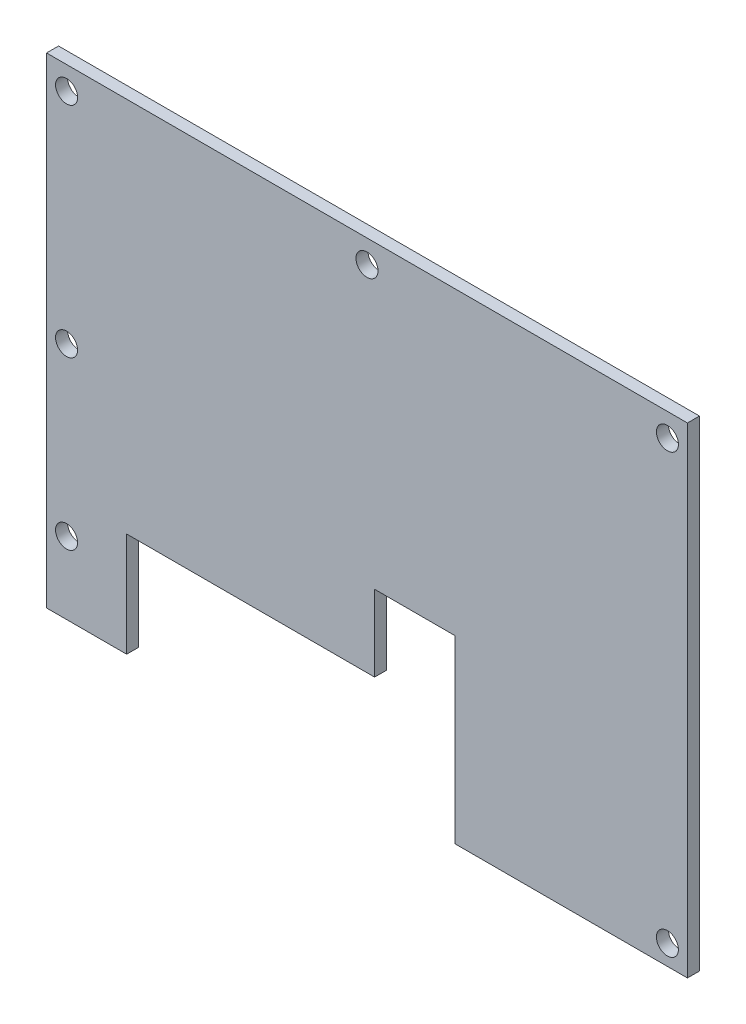
SolidWorks part; units mm, degrees
ref_plane "Front Plane" through (0, 0, 0) normal (0, 0, 1) x (1, 0, 0)
ref_plane "Top Plane" through (0, 0, 0) normal (0, 1, 0) x (1, 0, 0)
ref_plane "Right Plane" through (0, 0, 0) normal (1, 0, 0) x (0, 0, -1)
sketch "Sketch1" plane through (0, 0, 0) normal (0, 0, 1) x (1, 0, 0)
  line L1 (0, 0) -> (160, 0)
  line L2 (0, 0) -> (0, 120)
  line L3 (0, 120) -> (160, 120)
  line L4 (160, 0) -> (160, 120)
  dimension "D1" = 160
  dimension "D2" = 120
extrude "Boss-Extrude1" add sketch "Sketch1" along normal blind 3
sketch "Sketch2" plane through (0, 0, 3) normal (0, 0, 1) x (1, 0, 0)
  line L0 (0, 0) -> (160, 0) construction
  line L1 (81.9, 0) -> (102, 0)
  line L2 (81.9, 0) -> (81.9, 45)
  line L3 (81.9, 45) -> (102, 45)
  line L4 (102, 0) -> (102, 45)
  line L5 (160, 0) -> (160, 120) construction
  line L6 (0, 120) -> (0, 0) construction
  line L7 (20, 0) -> (81.9, 0)
  line L8 (20, 0) -> (20, 26)
  line L9 (20, 26) -> (81.9, 26)
  line L10 (81.9, 0) -> (81.9, 26)
  line M4 (0, 120) -> (0, 0)
  line M5 (0, 0) -> (160, 0)
  dimension "D1" = 20.1
  dimension "D2" = 58
  dimension "D3" = 45
  dimension "D4" = 26
  dimension "D5" = 20
extrude "Cut-Extrude1" cut sketch "Sketch2" against normal blind 10 contours L4 L3 L2 M5 | L9 L2 M4 M5 region at (91.95, 22.5, 3) region at (50.95, 13, 3)
sketch "Sketch3" plane through (0, 0, 3) normal (0, 0, 1) x (1, 0, 0)
  line L0 (160, 0) -> (160, 120) construction
  line L1 (5, 114.23) -> (155, 114.23) construction
  line L2 (5, 114.23) -> (5, 5) construction
  line L3 (5, 5) -> (155, 5) construction
  line L4 (155, 114.23) -> (155, 5) construction
  line L6 (0, 120) -> (0, 0) construction
  line L7 (102, 0) -> (160, 0) construction
  point P0 (5, 114.23)
  point P1 (155, 5)
  point P3 (155, 114.23)
  point P6 (80, 114.23)
  point P7 (5, 59.615)
  point P12 (5, 18)
  dimension "D1" = 5
  dimension "D2" = 109.23
  dimension "D3" = 5
  dimension "D4" = 5
  dimension "D5" = 13
hole_wizard "M5 Clearance Hole1" positions "Sketch3" profile "Sketch4" hole size "M5" standard "ANSI Metric" end condition through all
sketch "Sketch4" plane through (5, 114.23, 3) normal (1, 0, 0) x (0, -1, 0)
  line L0 (0, 0) -> (0, 3)
  line L1 (0, 3) -> (2.75, 3)
  line L2 (2.75, 3) -> (2.75, 0)
  line L5 (2.75, 0) -> (0, 0)
  line L11 (0, -6.35) -> (0, 107.95) construction
  dimension "Thru Hole Dia." = 5.5
  dimension "Thru Hole Depth" = 3
